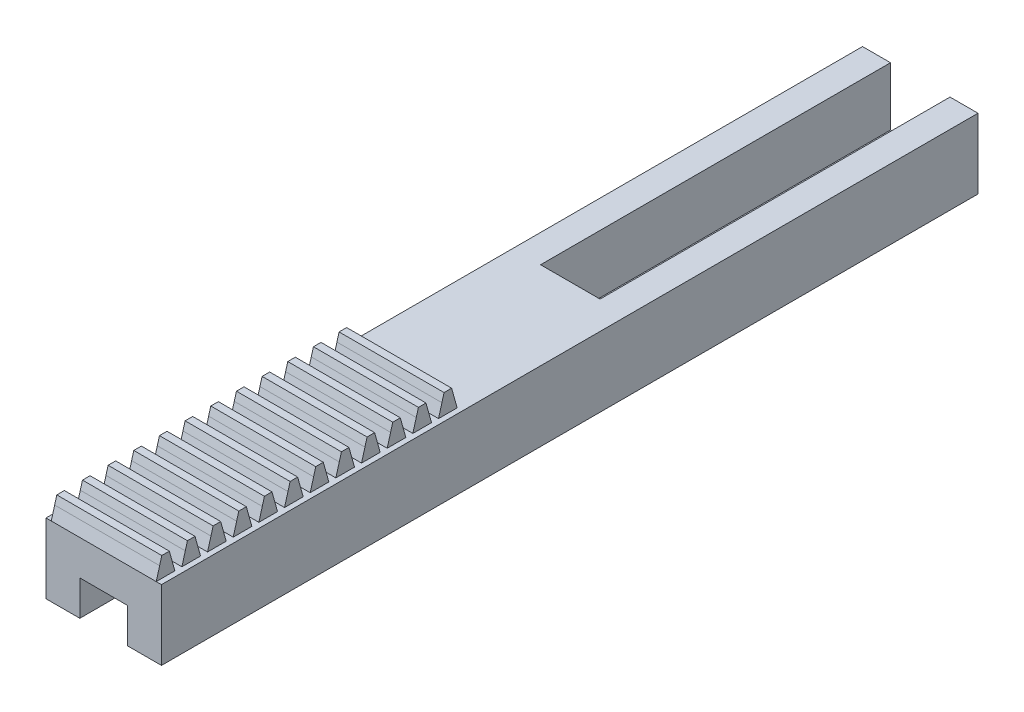
SolidWorks part; units mm, degrees
ref_plane "정면" through (0, 0, 0) normal (0, 0, 1) x (1, 0, 0)
ref_plane "윗면" through (0, 0, 0) normal (0, 1, 0) x (1, 0, 0)
ref_plane "우측면" through (0, 0, 0) normal (1, 0, 0) x (0, 0, -1)
sketch "스케치2" plane through (0, 0, 0) normal (1, 0, 0) x (0, 0, -1)
  line L0 (0, 0) -> (70, 0)
  line L1 (70, 0) -> (70, 6)
  line L2 (70, 6) -> (0, 6)
  line L3 (0, 6) -> (0, 0)
  line L4 (0, 6) -> (0.2918, 7.0378)
  line L5 (0.2918, 7.0378) -> (0.475, 7.7)
  line L6 (0.475, 7.7) -> (1.125, 7.7)
  line L7 (1.125, 7.7) -> (1.3082, 7.0378)
  line L8 (1.3082, 7.0378) -> (1.6, 6)
  line L9 (0.2918, 7.0378) -> (1.3082, 7.0378) construction
  dimension "D1" = 1.7
  dimension "D2" = 1.6
  dimension "D3" = 70
  dimension "D4" = 6
  dimension "D5" = 0.65
extrude "보스-돌출2" add sketch "스케치2" along normal mid plane 9.9 contours L2 L3 L0 L1 region at (0, 3, -35)
extrude "보스-돌출3" add sketch "스케치2<4>" along normal mid plane 9 contours L9 L4 L2 L8 | L5 L9 L7 L6 region at (0, 6.4803, -0.8) region at (0, 7.3446, -0.8)
sketch "스케치2<4>" plane through (0, 0, 0) normal (1, 0, 0) x (0, 0, -1) same geometry as "스케치2"
pattern_linear "선형 패턴1" count 12 spacing 2.2 along (0, 0, -1) of "보스-돌출3"
sketch "스케치3" plane through (0, 0, 0) normal (1, 0, 0) x (0, 0, -1)
  line L0 (0, 0) -> (70, 0) construction
  line L1 (0, 0) -> (35, 0)
  line L2 (0, 0) -> (0, 3)
  line L3 (0, 3) -> (35, 3)
  line L4 (35, 0) -> (35, 3)
  line L5 (0, 6) -> (0, 0) construction
  dimension "D1" = 3
  dimension "D2" = 35
sketch "스케치7" plane through (0, 6, 0) normal (0, 1, 0) x (1, 0, 0)
  line L0 (0, 55) -> (0, 0) construction
  line L1 (-2.55, 40) -> (2.55, 40)
  line L2 (-2.55, 40) -> (-2.55, 70)
  line L3 (-2.55, 70) -> (2.55, 70)
  line L4 (2.55, 40) -> (2.55, 70)
  line L5 (-2.55, 40) -> (2.55, 70) construction
  line L6 (-2.55, 70) -> (2.55, 40) construction
  line L7 (4.95, 70) -> (-4.95, 70) construction
  point P0 (0, 55)
  dimension "D1" = 5.1
  dimension "D2" = 30
extrude "컷-돌출1" cut sketch "스케치7" against normal blind 5
extrude "컷-돌출2" cut sketch "스케치3" against normal mid plane 4.1
